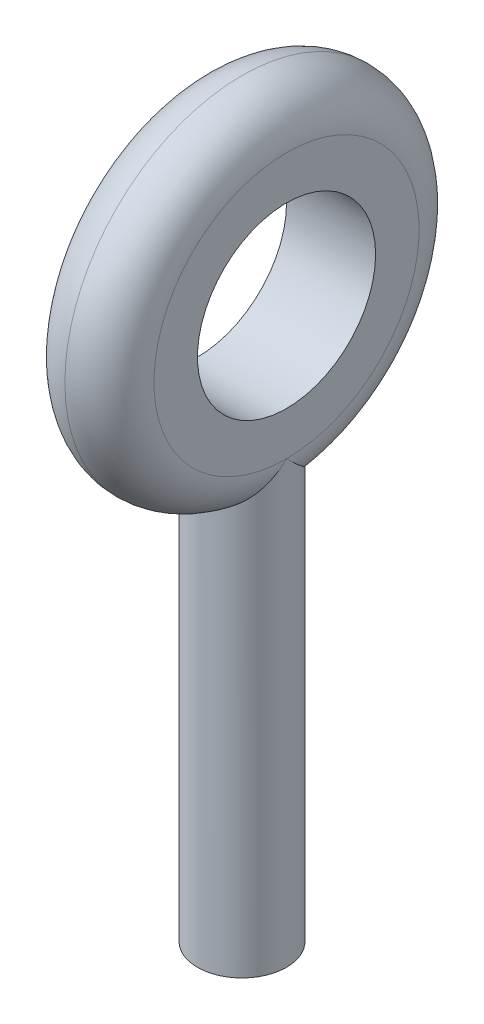
SolidWorks part; units mm, degrees
ref_plane "Front Plane" through (0, 0, 0) normal (0, 0, 1) x (1, 0, 0)
ref_plane "Top Plane" through (0, 0, 0) normal (0, 1, 0) x (1, 0, 0)
ref_plane "Right Plane" through (0, 0, 0) normal (1, 0, 0) x (0, 0, -1)
sketch "Sketch1" plane through (0, 0, 0) normal (1, 0, 0) x (0, 0, -1)
  circle A0 centre (0, 0) radius 6.35
  circle A1 centre (0, 0) radius 12.626
  dimension "D1" = 12.7
extrude "Boss-Extrude1" add sketch "Sketch1" along normal blind 6.35
sketch "Sketch3" plane through (6.35, 0, 0) normal (1, 0, 0) x (0, 0, -1)
  line L0 (-8.9948, -8.8606) -> (-8.9948, -15.4523)
  line L1 (-8.9948, -15.4523) -> (10.7986, -15.4523)
  line L2 (10.7986, -15.4523) -> (10.7986, -6.5427)
  line L3 (10.7986, -6.5427) -> (-8.9948, -6.5427)
  line L4 (-8.9948, -6.5427) -> (-8.9948, -8.8606)
  circle A0 centre (0, 0) radius 12.626 construction
extrude "Boss-Extrude2" add sketch "Sketch3" against normal blind 6.35
sketch "Sketch4" plane through (0, -15.4523, 0) normal (0, -1, 0) x (1, 0, 0)
  circle A0 centre (3.175, 0) radius 3.175
extrude "Boss-Extrude3" add sketch "Sketch4" along normal blind 50.8
sketch "Sketch5" plane through (6.35, 0, 0) normal (1, 0, 0) x (0, 0, -1)
  line L0 (-8.9948, -8.8606) -> (-8.9948, -15.4523)
  line L1 (-8.9948, -15.4523) -> (10.7986, -15.4523)
  line L2 (10.7986, -15.4523) -> (10.7986, -6.5427)
  arc A0 (-8.9948, -8.8606) -> (10.7986, -6.5427) centre (0, 0) ccw
extrude "Cut-Extrude1" cut sketch "Sketch5" against normal blind 6.35
sketch "Sketch7" plane through (0, -66.2523, 0) normal (0, -1, 0) x (1, 0, 0)
  circle A0 centre (3.175, 0) radius 3.175
extrude "Boss-Extrude4" add sketch "Sketch7" against normal blind 57.15
extrude "Cut-Extrude2" cut sketch "Sketch7<2>" against normal blind 25.4
sketch "Sketch7<2>" plane through (0, -66.2523, 0) normal (0, -1, 0) x (1, 0, 0) same geometry as "Sketch7"
fillet "Fillet1" radius 3.175 2 edges at (6.35, 0, -12.626) (0, 0, -12.626)
